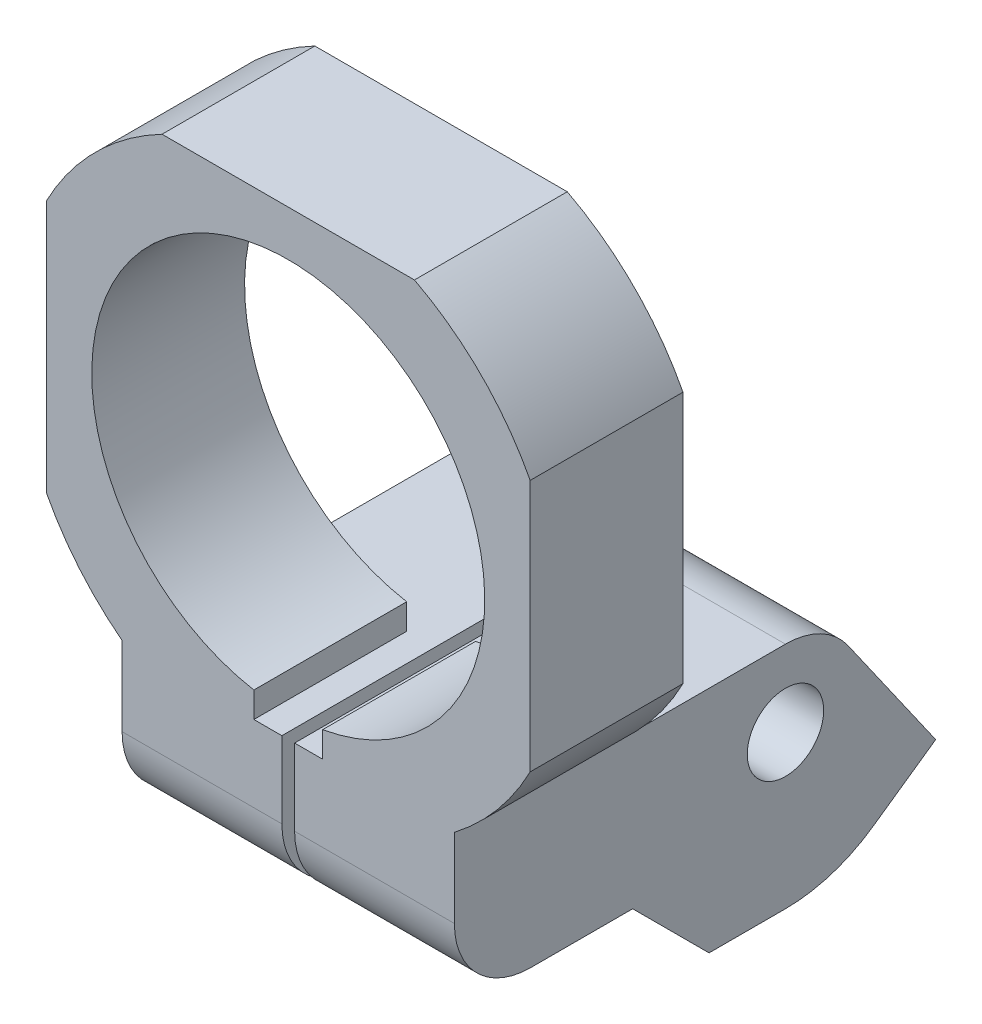
SolidWorks part; units mm, degrees
ref_plane "Front Plane" through (0, 0, 0) normal (0, 0, 1) x (1, 0, 0)
ref_plane "Top Plane" through (0, 0, 0) normal (0, 1, 0) x (1, 0, 0)
ref_plane "Right Plane" through (0, 0, 0) normal (1, 0, 0) x (0, 0, -1)
sketch "Sketch1" plane through (0, 0, 0) normal (0, 0, 1) x (1, 0, 0)
  line L0 (0, 11.4873) -> (0, -15.0157) construction
  line L1 (1.35, -8.5) -> (6.5239, -8.5)
  line L2 (1.35, -8.5) -> (-1.35, -8.5)
  line L3 (1.35, -8.5) -> (1.35, -7.4944)
  line L4 (1.35, -7.4944) -> (-1.35, -7.4944)
  line L5 (-1.35, -8.5) -> (-1.35, -7.4944)
  line L6 (1.35, -8.5) -> (-1.35, -7.4944) construction
  line L7 (1.35, -7.4944) -> (-1.35, -8.5) construction
  line L8 (-1.35, -8.5) -> (-6.5239, -8.5)
  line L9 (-1.35, -8.5) -> (-1.35, -14.6)
  line L10 (-1.35, -14.6) -> (-6.5239, -14.6)
  line L11 (-6.5239, -8.5) -> (-6.5239, -14.6)
  line L12 (1.35, -8.5) -> (1.35, -14.6)
  line L13 (-8.5, -8.5) -> (-1.25, -8.5)
  line L14 (-1.25, -8.5) -> (-1.25, -7.5117)
  line L15 (1.25, -7.5117) -> (1.25, -8.5)
  line L16 (1.25, -8.5) -> (8.5, -8.5)
  line L17 (8.5, -8.5) -> (8.5, -2.45)
  line L18 (8.5, -2.45) -> (10, -2.45)
  line L19 (10, 2.45) -> (8.5, 2.45)
  line L20 (8.5, 2.45) -> (8.5, 8.5)
  line L21 (8.5, 8.5) -> (-8.5, 8.5)
  line L22 (-8.5, 8.5) -> (-8.5, 2.45)
  line L23 (-8.5, 2.45) -> (-10, 2.45)
  line L24 (-10, -2.45) -> (-8.5, -2.45)
  line L25 (-8.5, -2.45) -> (-8.5, -8.5)
  line L26 (-8.5, -8.5) -> (-1.25, -8.5)
  line L27 (-1.25, -8.5) -> (-1.25, -7.5117)
  line L28 (1.25, -7.5117) -> (1.25, -8.5)
  line L29 (1.25, -8.5) -> (8.5, -8.5)
  line L30 (8.5, -8.5) -> (8.5, -2.45)
  line L31 (8.5, -2.45) -> (10, -2.45)
  line L32 (10, 2.45) -> (8.5, 2.45)
  line L33 (8.5, 2.45) -> (8.5, 8.5)
  line L34 (8.5, 8.5) -> (-8.5, 8.5)
  line L35 (-8.5, 8.5) -> (-8.5, 2.45)
  line L36 (-8.5, 2.45) -> (-10, 2.45)
  line L37 (-10, -2.45) -> (-8.5, -2.45)
  line L38 (-8.5, -2.45) -> (-8.5, -8.5)
  line L39 (1.35, -14.6) -> (6.5239, -14.6)
  line L40 (6.5239, -8.5) -> (6.5239, -14.6)
  line L41 (-1.25, -8.0059) -> (-1.35, -8.0059) construction
  line L42 (-1.35, -14.6) -> (-0.25, -14.6)
  line L43 (-1.35, -14.6) -> (-1.35, -8.6)
  line L44 (-1.35, -8.6) -> (-0.25, -8.6)
  line L45 (-0.25, -14.6) -> (-0.25, -8.6)
  line L46 (7.715, 0) -> (7.615, 0) construction
  line L47 (-1.25, -8.5) -> (-1.25, -8.6) construction
  line L48 (-1.35, -8.5) -> (1.35, -8.5)
  line L49 (-1.35, -8.5) -> (-1.35, -8.6)
  line L50 (-1.35, -8.6) -> (1.35, -8.6)
  line L51 (1.35, -8.5) -> (1.35, -8.6)
  line L52 (1.35, -8.6) -> (0.25, -8.6)
  line L53 (0.25, -14.6) -> (0.25, -8.6)
  line L54 (1.35, -14.6) -> (0.25, -14.6)
  circle A0 centre (0, 0) radius 7.715
  circle A1 centre (0, 0) radius 10.715
  arc A3 (1.25, -7.5117) -> (-1.25, -7.5117) centre (0, 0) ccw
  arc A4 (10, -2.45) -> (10, 2.45) centre (10, 0) ccw
  arc A5 (-10, 2.45) -> (-10, -2.45) centre (-10, 0) ccw
  arc A6 (1.25, -7.5117) -> (-1.25, -7.5117) centre (0, 0) ccw
  arc A7 (10, -2.45) -> (10, 2.45) centre (10, 0) ccw
  arc A8 (-10, 2.45) -> (-10, -2.45) centre (-10, 0) ccw
  point P10 (0, -7.9972)
  dimension "D2" = 0.1
  dimension "D4" = 3
  dimension "D3" = 0.5
  dimension "D5" = 6
  dimension "D1" = 0
extrude "Shape" add sketch "Sketch1" along normal blind 6 contours L36 A8 L37 L38 L26 L27 A0 L28 L29 L30 L31 A7 L32 L33 L34 L35 | A7 A1 L33 L32 | A7 L31 L30 A1 | A8 A1 L38 L37 | A8 L36 L35 A1 | L34 A1 | L8 A1 L9 | L12 A1 L1 | A1 L12 L39 L40 | A1 L11 L10 L9 | L9 A1 L45 L44 | A1 L43 L42 L45 | A1 L53 L54 L12 | L53 A1 L12 L50 region at (1.6235, -8.048, 0) region at (3.2599, -9.3092, 0) region at (4.1264, -12.177, 0) region at (0.7964, -9.6403, 0) region at (0.8019, -12.6401, 0) region at (9.2085, -3.9179, 0) region at (-3.2599, -9.3092, 0) region at (-0.7964, -9.6403, 0) region at (-0.8019, -12.6401, 0) region at (9.2085, 3.9179, 0) region at (-4.1264, -12.177, 0) region at (-9.2085, -3.9179, 0) region at (0, 9.3944, 0) region at (-9.2085, 3.9179, 0)
sketch "Sketch3" plane through (0, 0, 0) normal (0, 0, -1) x (-1, 0, 0)
  line L1 (-6.5239, -14.6) -> (-0.25, -14.6)
  line L2 (-6.5239, -14.6) -> (-6.5239, -8.6)
  line L3 (-6.5239, -8.6) -> (-0.25, -8.6)
  line L4 (-0.25, -14.6) -> (-0.25, -8.6)
  line L5 (6.5239, -14.6) -> (0.25, -14.6)
  line L6 (6.5239, -14.6) -> (6.5239, -8.6)
  line L7 (6.5239, -8.6) -> (0.25, -8.6)
  line L8 (0.25, -14.6) -> (0.25, -8.6)
extrude "Lever" add sketch "Sketch3" along normal blind 10
sketch "Sketch2" plane through (6.5239, 0, 0) normal (1, 0, 0) x (0, 0, -1)
  line L0 (-6, -11.6) -> (10, -11.6) construction
  line L4 (10, -8.6) -> (0, -8.6) construction
  line L5 (10, -8.6) -> (-6, -8.6)
  line L6 (10, -8.6) -> (10, -14.6)
  line L7 (10, -14.6) -> (-6, -14.6)
  line L8 (-6, -8.6) -> (-6, -14.6)
  circle A0 centre (7, -11.6) radius 3
  circle A1 centre (7, -11.6) radius 1.5
  circle A2 centre (-3, -11.6) radius 3
  line M4 (-6, -14.6) -> (10, -14.6)
  line M9 (10, -14.6) -> (10, -8.6)
  line M10 (10, -8.6) -> (0, -8.6)
  dimension "D1" = 3
extrude "Cuts" cut sketch "Sketch2" against normal up to surface (13.0478 mm away) contours A0 L6 M10 | A0 L7 M9 | L0 A1 | A1 L0 | A2 L8 M4 region at (6.5239, -13.9299, 5.3299) region at (6.5239, -13.9299, -9.3299) region at (6.5239, -10.9634, -7) region at (6.5239, -12.2366, -7) region at (6.5239, -9.2701, -9.3299) up to face at (-6.5239, -10.5667, -1.3333)
sketch "Sketch5" plane through (-6.5239, 0, 0) normal (-1, 0, 0) x (0, 0, 1)
  line L0 (-7, -17.6) -> (-4, -17.6)
  line L1 (-4, -17.6) -> (-4, -14.6)
  line L2 (3, -14.6) -> (-7, -14.6) construction
  line L3 (-7, -11.6) -> (-10.4415, -16.5149)
  line L4 (-7, -11.6) -> (-7, -14.6) construction
  line L5 (-10.4415, -16.5149) -> (-12.8989, -14.7942)
  line L6 (-12.8989, -14.7942) -> (-9.4575, -9.8793)
  line L7 (-7, -17.6) -> (-7, -14.6)
  line L8 (-4, -17.6) -> (-1, -14.6)
  circle A0 centre (-7, -11.6) radius 6
  arc A1 (-7, -8.6) -> (-7, -14.6) centre (-7, -11.6) ccw construction
  arc M8 (-7, -8.6) -> (-7, -14.6) centre (-7, -11.6) ccw
  line M9 (-7, -14.6) -> (3, -14.6)
  dimension "D1" = 12
  dimension "D2" = 45
  dimension "D3" = 35
extrude "Limits 1" add sketch "Sketch5" against normal up to surface (6.2739 mm away) contours A0 L0 L1 | L7 A0 L1 M9 | L6 A0 L3 M8 | A0 L6 L5 | L3 A0 L7 M8 | A0 L1 L8 M9 | L1 A0 M9 region at (-6.5239, -17.3619, -4.7396) region at (-6.5239, -15.9818, -8.3816) region at (-6.5239, -15.9801, -5.5723) region at (-6.5239, -15.9486, -2.6514) region at (-6.5239, -13.951, -10.5987) region at (-6.5239, -15.0233, -12.1565) region at (-6.5239, -15.3955, -3.2045) up to face at (-0.25, -11.6, -5.5)
sketch "Sketch6" plane through (6.5239, 0, 0) normal (1, 0, 0) x (0, 0, -1)
  line L0 (-3, -14.6) -> (7, -14.6) construction
  line L1 (-3, -14.6) -> (7, -14.6)
  line L7 (-3, -14.6) -> (1, -14.6)
  line L8 (1, -14.6) -> (4, -17.6)
  line L9 (4, -17.6) -> (7, -17.6)
  line L10 (10.4415, -16.5149) -> (12.8989, -14.7942)
  line L11 (12.8989, -14.7942) -> (9.4575, -9.8793)
  line L12 (7, -8.6) -> (-6, -8.6)
  line L13 (-6, -8.6) -> (-6, -11.6)
  line L14 (-3, -14.6) -> (1, -14.6)
  line L15 (1, -14.6) -> (4, -17.6)
  line L16 (4, -17.6) -> (7, -17.6)
  line L17 (10.4415, -16.5149) -> (12.8989, -14.7942)
  line L18 (12.8989, -14.7942) -> (9.4575, -9.8793)
  line L19 (7, -8.6) -> (-6, -8.6)
  line L20 (-6, -8.6) -> (-6, -11.6)
  arc A0 (7, -14.6) -> (7, -8.6) centre (7, -11.6) ccw construction
  arc A1 (7, -14.6) -> (7, -8.6) centre (7, -11.6) ccw
  arc A3 (7, -17.6) -> (10.4415, -16.5149) centre (7, -11.6) ccw
  arc A4 (9.4575, -9.8793) -> (7, -8.6) centre (7, -11.6) ccw
  arc A5 (-6, -11.6) -> (-3, -14.6) centre (-3, -11.6) ccw
  arc A6 (7, -17.6) -> (10.4415, -16.5149) centre (7, -11.6) ccw
  arc A7 (9.4575, -9.8793) -> (7, -8.6) centre (7, -11.6) ccw
  arc A8 (-6, -11.6) -> (-3, -14.6) centre (-3, -11.6) ccw
  arc M13 (7, -14.6) -> (7, -8.6) centre (7, -11.6) ccw
  dimension "D1" = 0
extrude "Limits 2" add sketch "Sketch6" against normal up to surface (6.2739 mm away) contours L16 A6 L17 L18 L1 M13 region at (6.5239, -15.3081, -7.6258) up to face at (0.25, -13.1, -7)
sketch "Sketch8" plane through (0, 0, 6) normal (0, 0, 1) x (1, 0, 0)
  line L1 (-9.5, -9.5) -> (9.5, -9.5)
  line L2 (-9.5, -9.5) -> (-9.5, 9.5)
  line L3 (-9.5, 9.5) -> (9.5, 9.5)
  line L4 (9.5, -9.5) -> (9.5, 9.5)
  line L5 (-9.5, -9.5) -> (9.5, 9.5) construction
  line L6 (-9.5, 9.5) -> (9.5, -9.5) construction
  line L7 (-10.715, -10.715) -> (10.715, -10.715)
  line L8 (-10.715, -10.715) -> (-10.715, 10.715)
  line L9 (-10.715, 10.715) -> (10.715, 10.715)
  line L10 (10.715, -10.715) -> (10.715, 10.715)
  line L11 (-10.715, -10.715) -> (10.715, 10.715) construction
  line L12 (-10.715, 10.715) -> (10.715, -10.715) construction
  arc A0 (6.5239, -8.5) -> (-6.5239, -8.5) centre (0, 0) ccw construction
  point P0 (0, 0)
  point P6 (0, 0)
  arc M16 (6.5239, -8.5) -> (-6.5239, -8.5) centre (0, 0) ccw
  dimension "D1" = 19
extrude "Cut-Extrude2" cut sketch "Sketch8" against normal up to next contours L3 M16 | L2 M16 | L4 M16 region at (-9.9884, 0, 6) region at (9.9884, 0, 6) region at (0, 9.9884, 6)
